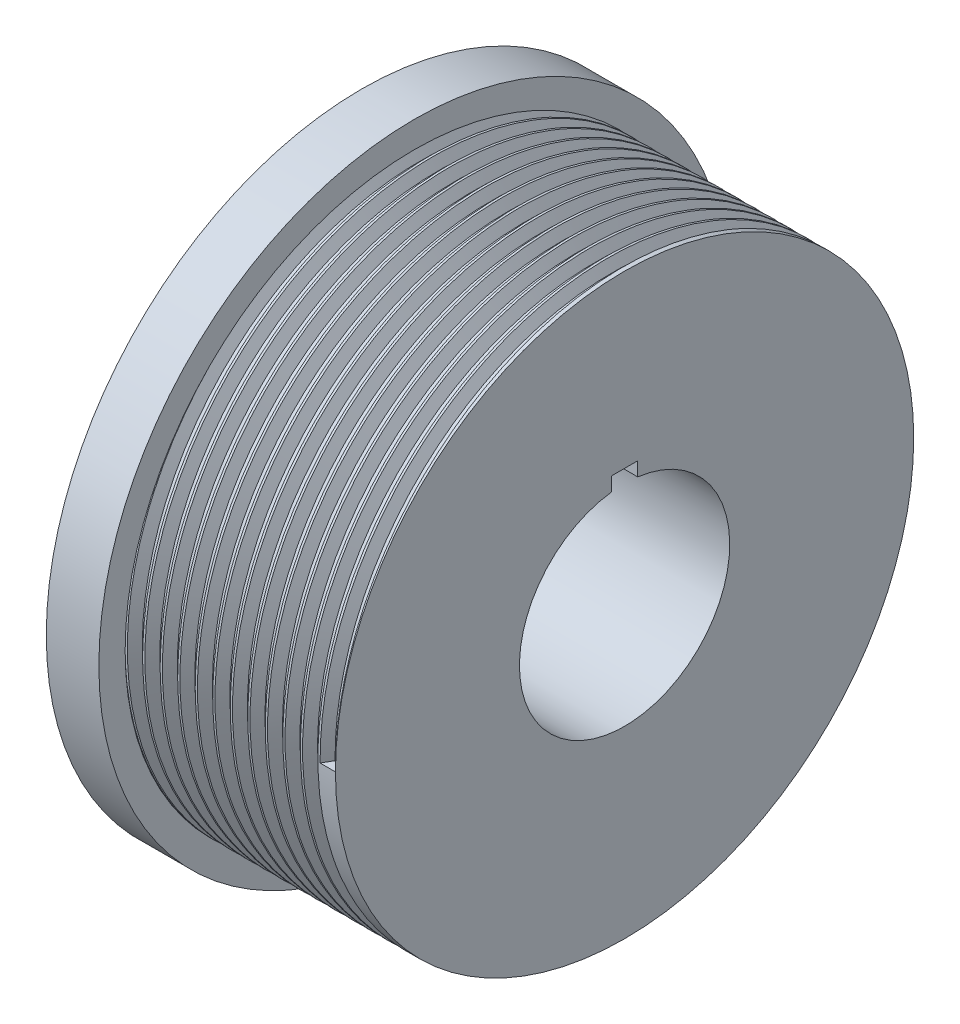
SolidWorks part; units mm, degrees
ref_plane "Front Plane" through (0, 0, 0) normal (0, 0, 1) x (1, 0, 0)
ref_plane "Top Plane" through (0, 0, 0) normal (0, 1, 0) x (1, 0, 0)
ref_plane "Right Plane" through (0, 0, 0) normal (1, 0, 0) x (0, 0, -1)
sketch "Sketch1" plane through (0, 0, 0) normal (1, 0, 0) x (0, 0, -1)
  line L0 (-0.7937, 6.3002) -> (-0.7937, 7.1437)
  line L1 (-0.7937, 7.1437) -> (0.7937, 7.1437)
  line L2 (0.7937, 7.1437) -> (0.7937, 6.3002)
  circle A0 centre (0, 0) radius 19.05
  circle A1 centre (0, 0) radius 17.4625
  arc A2 (-0.7937, 6.3002) -> (0.7937, 6.3002) centre (0, 0) ccw
  point P13 (0, 7.1437)
  dimension "D1" = 34.925
  dimension "D2" = 38.1
  dimension "D5" = 12.7
  dimension "D3" = 1.5875
  dimension "D4" = 7.1437
extrude "Boss-Extrude1" add sketch "Sketch1" along normal blind 3.175 contours A0 A1 region at (0, 0, 18.5112)
extrude "Boss-Extrude2" add sketch "Sketch1<2>" along normal blind 15.875 contours A1 region at (0, 0, 16.9686)
sketch "Sketch1<2>" plane through (0, 0, 0) normal (1, 0, 0) x (0, 0, -1) same geometry as "Sketch1"
thread "Thread1" pitch 1.0583 method cut profile "Thread Profile1" start angle 0, offset 0, length 0, pitch 1.0583, diameter 34.925
ref_plane "Plane1" through (15.875, 0, 17.4625) normal (0, -1, 0) x (0, 0, 1)
sketch "Thread Profile1" plane through (15.875, 0, 17.4625) normal (0, -1, 0) x (0, 0, 1)
  line L0 (0, 0) -> (0, 1.0583) construction
  line L11 (0, 0) -> (0, 0.926)
  line L12 (0, 0.926) -> (-0.5728, 0.5953)
  line L13 (-0.5728, 0.5953) -> (-0.5728, 0.3307)
  line L15 (-0.5728, 0.3307) -> (0, 0)
  line L17 (-0.5728, 0.463) -> (0, 0.463) construction
  point P2 (0, 0)
  dimension "Pitch" = 1.0583
  dimension "Profile_Angle" = 60
  dimension "Profile_Land" = 0.2646
  dimension "Profile_Height" = 0.5728
